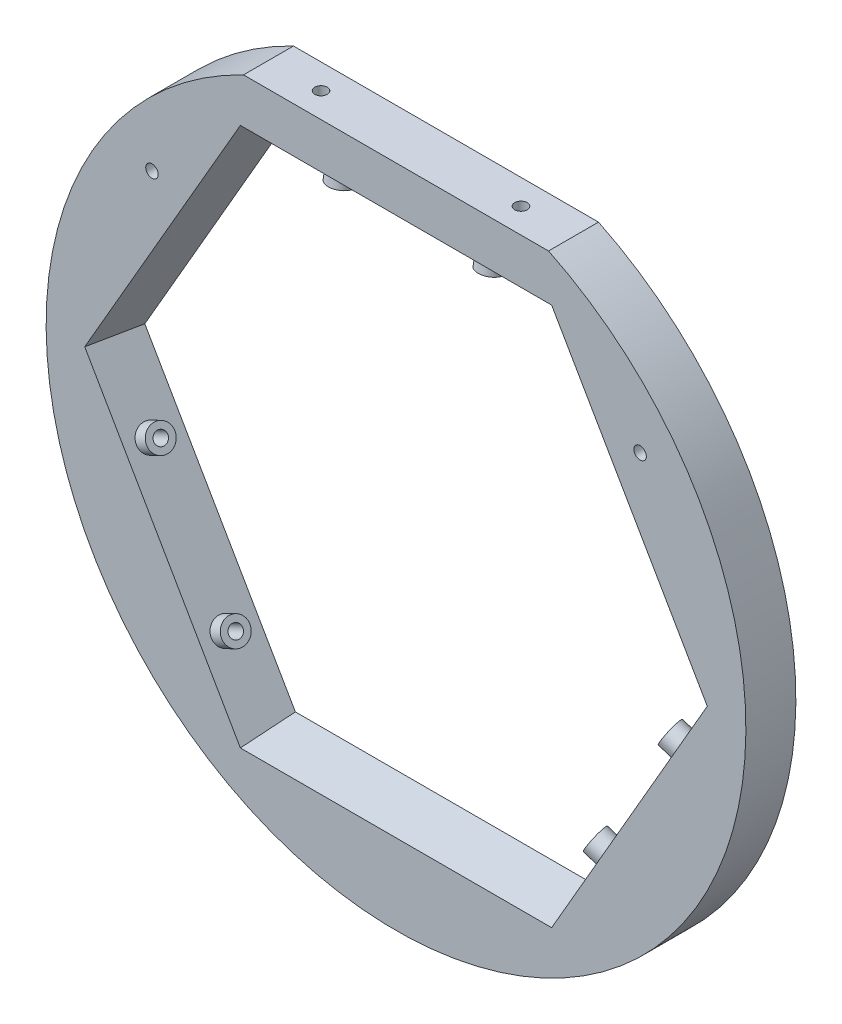
SolidWorks part; units mm, degrees
ref_plane "Plan de face" through (0, 0, 0) normal (0, 0, 1) x (1, 0, 0)
ref_plane "Plan de dessus" through (0, 0, 0) normal (0, 1, 0) x (1, 0, 0)
ref_plane "Plan de droite" through (0, 0, 0) normal (1, 0, 0) x (0, 0, -1)
sketch "Esquisse1" plane through (0, 0, 0) normal (0, 0, 1) x (1, 0, 0)
  line L1 (60.258, 0) -> (30.129, 52.185)
  line L2 (30.129, 52.185) -> (-30.129, 52.185)
  line L3 (-30.129, 52.185) -> (-60.258, 0)
  line L4 (-60.258, 0) -> (-30.129, -52.185)
  line L5 (-30.129, -52.185) -> (30.129, -52.185)
  line L6 (30.129, -52.185) -> (60.258, 0)
  circle A0 centre (0, 0) radius 70
  circle A1 centre (0, 0) radius 52.185 construction
  dimension "D1" = 140
  dimension "D2" = 104.37
extrude "Boss.-Extru.1" add sketch "Esquisse1" along normal blind 10
chamfer "Chanfrein1" distance 1.7471 angle 80.09 6 edges at (-45.1935, 26.0925, 10) (-45.1935, -26.0925, 10) (0, -52.185, 10) (45.1935, -26.0925, 10) (45.1935, 26.0925, 10) (0, 52.185, 10) first distance on face at (70, 0, 10)
sketch "Esquisse2" plane through (-43.855, -25.3197, -8.8471) normal (0.8531, 0.4925, 0.1721) x (0.149, 0.0861, -0.9851)
  line L0 (-8.9811, 0) -> (-19.1326, 0) construction
  line L1 (-8.9811, 30.129) -> (-8.9811, -30.129) construction
  line L2 (-19.1326, -31.1377) -> (-19.1326, 31.1377) construction
  line L3 (-14.6368, 15) -> (-14.6368, -15) construction
  circle A0 centre (-14.6368, 15) radius 1.25
  circle A1 centre (-14.6368, -15) radius 1.25
  point P12 (-14.6368, 0)
  point P13 (-14.0568, 0)
  dimension "D1" = 2.5
  dimension "D2" = 0.58
  dimension "D3" = 15
extrude "Enlèv. mat.-Extru.1" cut sketch "Esquisse2" against normal blind 8
sketch "Esquisse3" plane through (-43.855, -25.3197, -8.8471) normal (0.8531, 0.4925, 0.1721) x (0.149, 0.0861, -0.9851)
  circle A0 centre (-14.6368, -15) radius 2.5
  circle A1 centre (-14.6368, 15) radius 2.5
  circle A2 centre (-14.6368, -15) radius 1.25 construction
  circle A3 centre (-14.6368, 15) radius 1.25 construction
  circle A4 centre (-14.6368, -15) radius 1.25
  circle A5 centre (-14.6368, 15) radius 1.25
  dimension "D1" = 5
extrude "Boss.-Extru.2" add sketch "Esquisse3" along normal blind 3
pattern_circular "Répétition circulaire1" count 3 over 360 about axis through (0, 0, 0) along (0, 0, 1) of "Enlèv. mat.-Extru.1", "Boss.-Extru.2"
sketch "Esquisse4" plane through (0, 0, 0) normal (0, 0, -1) x (-1, 0, 0)
  line L0 (30.5123, 63) -> (-30.5123, 63)
  circle A0 centre (0, 0) radius 70 construction
  arc A1 (30.5123, 63) -> (-30.5123, 63) centre (0, 0) ccw
  dimension "D1" = 61.0246
extrude "Enlèv. mat.-Extru.2" cut sketch "Esquisse4" against normal up to next
sketch "Esquisse5" plane through (0, 63, 0) normal (0, 1, 0) x (1, 0, 0)
  line L0 (-30.5123, -10) -> (-30.5123, 0) construction
  line L1 (-20, -5) -> (20, -5) construction
  line L4 (30.5123, -10) -> (-30.5123, -10) construction
  circle A0 centre (-20, -5) radius 1.25
  circle A1 centre (20, -5) radius 1.25
  point P4 (0, -5)
  point P9 (-30.5123, -5)
  point P10 (0, -10)
  dimension "D1" = 2.5
  dimension "D2" = 40
extrude "Enlèv. mat.-Extru.3" cut sketch "Esquisse5" against normal blind 8
sketch "Esquisse6" plane through (0, 0, 0) normal (0, 0, -1) x (-1, 0, 0)
  line L0 (48.8237, 37.185) -> (-48.8237, 37.185) construction
  line L1 (-30.129, 52.185) -> (30.129, 52.185) construction
  line L2 (56.3494, 41.53) -> (41.2979, 32.84) construction
  line L3 (30.129, 52.185) -> (60.258, 0) construction
  line L4 (-41.2979, 32.84) -> (-56.3494, 41.53) construction
  line L5 (-60.258, 0) -> (-30.129, 52.185) construction
  circle A0 centre (48.8237, 37.185) radius 1.25
  circle A1 centre (-48.8237, 37.185) radius 1.25
  arc A2 (-30.5123, 63) -> (30.5123, 63) centre (0, 0) ccw construction
  point P18 (-48.8237, 37.185)
  point P19 (48.8237, 37.185)
  dimension "D2" = 2.5
  dimension "D1" = 15
extrude "Enlèv. mat.-Extru.4" cut sketch "Esquisse6" against normal up to next
